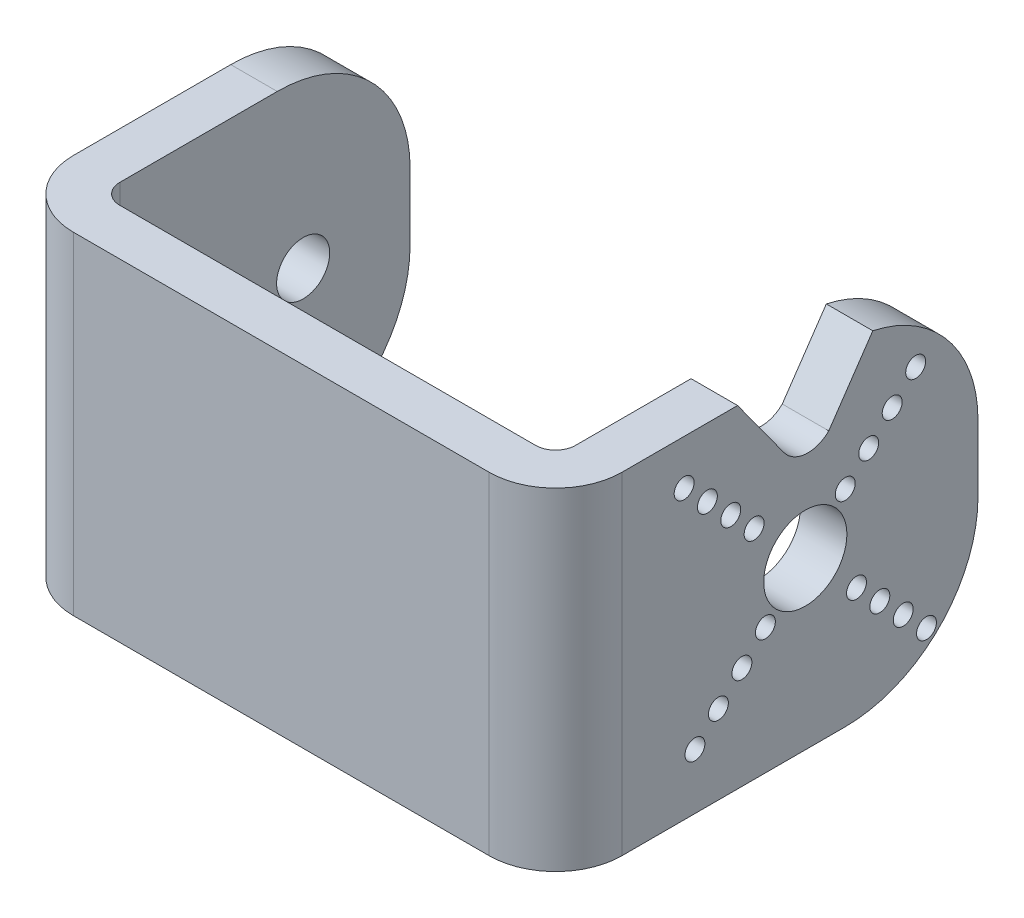
SolidWorks part; units mm, degrees
ref_plane "Front Plane" through (0, 0, 0) normal (0, 0, 1) x (1, 0, 0)
ref_plane "Top Plane" through (0, 0, 0) normal (0, 1, 0) x (1, 0, 0)
ref_plane "Right Plane" through (0, 0, 0) normal (1, 0, 0) x (0, 0, -1)
sketch "Sketch1" plane through (0, 0, 0) normal (0, 1, 0) x (1, 0, 0)
  line L0 (-56.3757, 54.198) -> (-56.3757, 10.498)
  line L1 (26.2243, 64.098) -> (26.2243, 10.498)
  line L2 (-46.3757, 0.498) -> (16.2243, 0.498)
  line L3 (-49.3757, 54.198) -> (-49.3757, 10.498)
  line L4 (-46.3757, 7.498) -> (16.2243, 7.498)
  line L5 (19.2243, 64.098) -> (19.2243, 10.498)
  line L6 (19.2243, 64.098) -> (26.2243, 64.098)
  line L7 (-49.3757, 54.198) -> (-56.3757, 54.198)
  arc A0 (-56.3757, 10.498) -> (-46.3757, 0.498) centre (-46.3757, 10.498) ccw
  arc A1 (16.2243, 0.498) -> (26.2243, 10.498) centre (16.2243, 10.498) ccw
  arc A2 (-49.3757, 10.498) -> (-46.3757, 7.498) centre (-46.3757, 10.498) ccw
  arc A3 (16.2243, 7.498) -> (19.2243, 10.498) centre (16.2243, 10.498) ccw
  dimension "D1" = 10
  dimension "D3" = 10
  dimension "D2" = 82.6
  dimension "D4" = 46.7
  dimension "D6" = 63.6
  dimension "D5" = 7
extrude "Boss-Extrude1" add sketch "Sketch1" along normal blind 50
fillet "Fillet2" radius 20 4 edges at (-52.8757, 50, -54.198) (-52.8757, 0, -54.198) (22.7243, 0, -64.098) (22.7243, 50, -64.098)
sketch "Sketch6" plane through (26.2243, 0, 0) normal (1, 0, 0) x (0, 0, -1)
  line L0 (64.098, 30) -> (64.098, 20) construction
  line L1 (85.3454, 25) -> (-15.2119, 25) construction
  circle A0 centre (38.098, 25) radius 4
  point P5 (64.098, 25)
  line B0 (19.0389, 5.9409) -> (56.3034, 43.2054) construction
  line B1 (-1276.2531, -1372.4722) -> (-849.632, -945.8511) construction
  line B2 (19.1731, 5.8923) -> (56.5233, 42.9855) construction
  line B3 (-122.2936, 133.0666) -> (-69.2606, 186.0996) construction
  line B4 (33.6703, 29.4276) -> (42.5256, 20.5724) construction
  line B5 (19.8546, 43.2434) -> (59.051, 4.047) construction
  circle B6 centre (19.8546, 43.2434) radius 1.5
  circle B7 centre (23.3548, 39.7432) radius 1.5
  circle B8 centre (26.8762, 36.2218) radius 1.5
  circle B9 centre (30.3905, 32.7075) radius 1.5
  circle B10 centre (32.0876, 18.9896) radius 1.5
  circle B11 centre (28.552, 15.4541) radius 1.5
  circle B12 centre (25.0165, 11.9185) radius 1.5
  circle B13 centre (21.481, 8.383) radius 1.5
  circle B14 centre (38.098, 25) radius 6.2616
  circle B15 centre (-8.1988, -9.2742) radius 3.25 construction
  circle B16 centre (3.822, -21.295) radius 3.25 construction
  circle B17 centre (44.8342, 43.7588) radius 3.25 construction
  circle B18 centre (56.855, 31.738) radius 3.25 construction
  circle B19 centre (44.1084, 31.0104) radius 1.5
  circle B20 centre (47.6439, 34.5459) radius 1.5
  circle B21 centre (51.1795, 38.0815) radius 1.5
  circle B22 centre (54.715, 41.617) radius 1.5
  circle B23 centre (56.3413, 6.7566) radius 1.5
  circle B24 centre (52.8412, 10.2568) radius 1.5
  circle B25 centre (49.3198, 13.7782) radius 1.5
  circle B26 centre (45.8054, 17.2925) radius 1.5
  dimension "D2" = 8
  dimension "D1" = 26
sketch_block_instance "Block-Sketch2-2"
sketch_block "Block-Sketch2" parameters "D2"=3, "D3"=3, "D4"=3, "D5"=3, "D6"=3, "D7"=3, "D8"=3, "D9"=3, "D10"=6.5, "D11"=6.5, "D12"=6.5, "D1"=52.7, "D13"=75, "D14"=17, "D15"=75, "D16"=8.5, "D17"=13.5, "D18"=18.5, "D19"=23.5, "D20"=10.9, "D21"=15.87, "D22"=20.85, "D23"=25.8
extrude "Cut-Extrude2" cut sketch "Sketch6" against normal blind 28.4 contours A0 L1 | L1 A0 | L1 B14 A0 | B14 L1 A0 | B9 | B8 | B7 | B6 | B19 | B20 | B21 | B22 | B26 | B25 | B24 | B23 | B10 | B11 | B12 | B13 region at (26.2243, 18.8784, -38.098) region at (26.2243, 25.14, -43.2288) region at (26.2243, 23.3023, -38.098) region at (26.2243, 26.6977, -38.098) region at (26.2243, 43.2434, -19.8546) region at (26.2243, 39.7432, -23.3548) region at (26.2243, 36.2218, -26.8762) region at (26.2243, 32.7075, -30.3905) region at (26.2243, 18.9896, -32.0876) region at (26.2243, 15.4541, -28.552) region at (26.2243, 11.9185, -25.0165) region at (26.2243, 8.383, -21.481) region at (26.2243, 31.0104, -44.1084) region at (26.2243, 34.5459, -47.6439) region at (26.2243, 38.0815, -51.1795) region at (26.2243, 41.617, -54.715) region at (26.2243, 6.7566, -56.3413) region at (26.2243, 10.2568, -52.8412) region at (26.2243, 13.7782, -49.3198) region at (26.2243, 17.2925, -45.8054)
extrude "Cut-Extrude3" cut sketch "Sketch6<3>" against normal blind 136.4 contours L1 A0 | A0 L1 region at (26.2243, 23.3023, -38.098) region at (26.2243, 26.6977, -38.098)
sketch "Sketch6<3>" plane through (26.2243, 0, 0) normal (1, 0, 0) x (0, 0, -1) same geometry as "Sketch6"
sketch "Sketch7" plane through (26.2243, 0, 0) normal (1, 0, 0) x (0, 0, -1)
  line L0 (27.9014, 50) -> (34.8899, 40.3636)
  line L1 (10.498, 50) -> (44.098, 50) construction
  line L2 (41.6295, 39.8302) -> (48.2623, 49.5617)
  arc A0 (34.8899, 40.3636) -> (41.6295, 39.8302) centre (38.4873, 42.9724) ccw
  arc A1 (64.098, 30) -> (44.098, 50) centre (44.098, 30) ccw construction
  arc M16 (64.098, 30) -> (44.098, 50) centre (44.098, 30) ccw
  line M17 (44.098, 50) -> (10.498, 50)
extrude "Cut-Extrude4" cut sketch "Sketch7" against normal blind 26.4 and the other way through all contours L0 A0 L2 M16 M17 region at (26.2243, 45.5364, -38.2869)
equation "\"D3@Sketch1\"=\"D1@Sketch1\""
